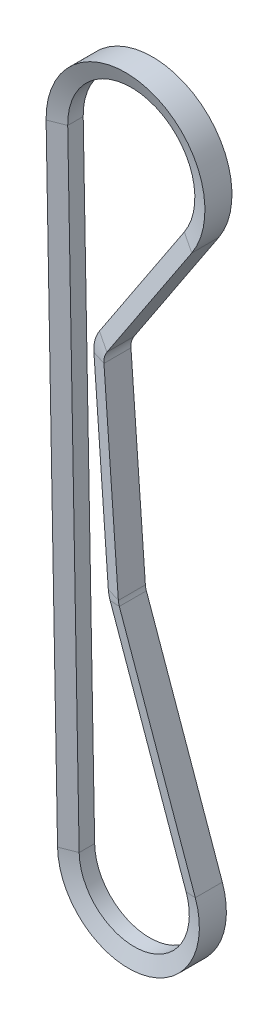
SolidWorks part; units mm, degrees
ref_plane "Front Plane" through (0, 0, 0) normal (0, 0, 1) x (1, 0, 0)
ref_plane "Top Plane" through (0, 0, 0) normal (0, 1, 0) x (1, 0, 0)
ref_plane "Right Plane" through (0, 0, 0) normal (1, 0, 0) x (0, 0, -1)
sketch "Sketch2" plane through (0, 0, 0) normal (0, 0, 1) x (1, 0, 0)
  line L0 (0, 0) -> (1, 0) construction
  line L1 (0, 0) -> (0, 1) construction
  line L12 (-24.9958, -0.4588) -> (-29.0332, 219.4836)
  line L14 (22.3138, 204.5477) -> (-7.6004, 159.3337)
  line L15 (-8.6379, 155.3695) -> (-3.5625, 85.5537)
  line L16 (-3.2143, 83.8925) -> (23.5633, 8.3528)
  arc A4 (-29.0332, 219.4836) -> (22.3138, 204.5477) centre (-1.0379, 219.9976) cw
  arc A7 (23.5633, 8.3528) -> (-24.9958, -0.4588) centre (0, 0) cw
  arc A8 (-7.6004, 159.3337) -> (-8.6379, 155.3695) centre (-2.3046, 155.8299) ccw
  arc A9 (-3.5625, 85.5537) -> (-3.2143, 83.8925) centre (2.7708, 86.0141) ccw
ref_plane "Plane4" through (23.5633, 8.3528, 0) normal (0.3341, -0.9425, 0) x (-0.9425, -0.3341, 0)
sketch "Sketch3" plane through (23.5633, 8.3528, 0) normal (0.3341, -0.9425, 0) x (-0.9425, -0.3341, 0)
  line L0 (0, -4.7625) -> (0, 4.7625)
  line L1 (0, -4.7625) -> (5.588, -2.7286)
  line L2 (5.588, -2.7286) -> (5.588, 2.7286)
  line L3 (5.588, 2.7286) -> (0, 4.7625)
  line L4 (0, 0) -> (5.588, 0) construction
  dimension "D1" = 9.525
  dimension "D2" = 5.588
  dimension "D3" = 40
sweep "Sweep1" add profiles "Sketch3" path "Sketch2"
